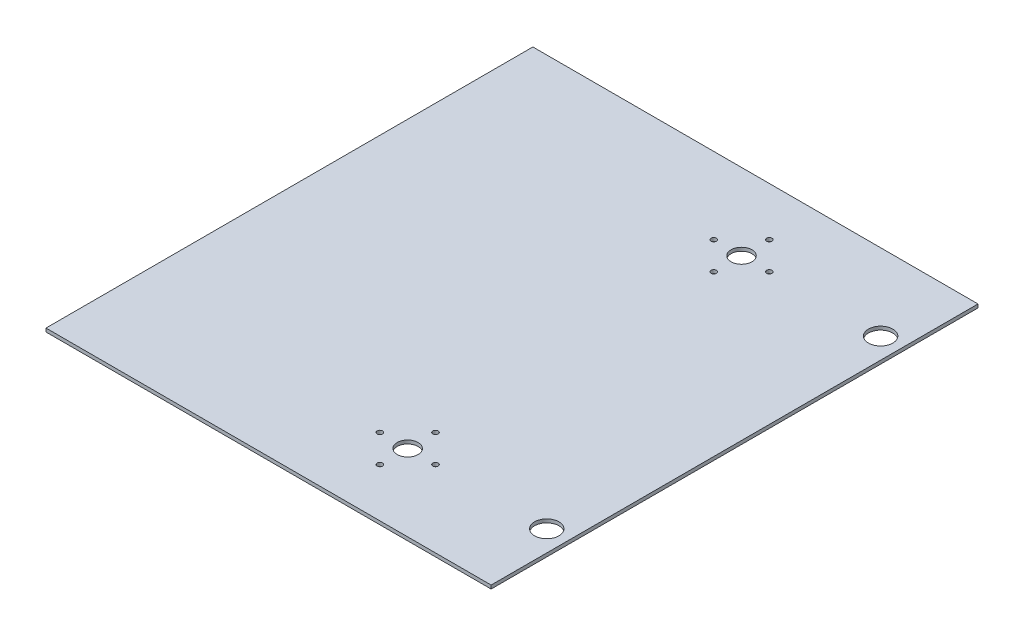
SolidWorks part; units mm, degrees
material "6061 Alloy"
ref_plane "Front Plane" through (0, 0, 0) normal (0, 0, 1) x (1, 0, 0)
ref_plane "Top Plane" through (0, 0, 0) normal (0, 1, 0) x (1, 0, 0)
ref_plane "Right Plane" through (0, 0, 0) normal (1, 0, 0) x (0, 0, -1)
sketch "Sketch1" plane through (0, 0, 0) normal (0, 1, 0) x (1, 0, 0)
  line L1 (203.2, -222.25) -> (-203.2, -222.25)
  line L2 (203.2, -222.25) -> (203.2, 222.25)
  line L3 (203.2, 222.25) -> (-203.2, 222.25)
  line L4 (-203.2, -222.25) -> (-203.2, 222.25)
  line L5 (203.2, -222.25) -> (-203.2, 222.25) construction
  line L6 (203.2, 222.25) -> (-203.2, -222.25) construction
  point P0 (0, 0)
  dimension "D1" = 406.4
  dimension "D2" = 444.5
extrude "Boss-Extrude1" add sketch "Sketch1" along normal blind 3.175
sketch "Sketch3" plane through (0, 3.175, 0) normal (0, 1, 0) x (1, 0, 0)
  arc A0 (66.675, -152.4) -> (47.625, -152.4) centre (57.15, -152.4) ccw construction
  arc A1 (47.625, -152.4) -> (66.675, -152.4) centre (57.15, -152.4) ccw construction
  arc A2 (66.675, -152.4) -> (47.625, -152.4) centre (57.15, -152.4) ccw
  arc A3 (47.625, -152.4) -> (66.675, -152.4) centre (57.15, -152.4) ccw
  arc A4 (66.675, 152.4) -> (47.625, 152.4) centre (57.15, 152.4) ccw construction
  arc A5 (47.625, 152.4) -> (66.675, 152.4) centre (57.15, 152.4) ccw construction
  arc A6 (66.675, 152.4) -> (47.625, 152.4) centre (57.15, 152.4) ccw
  arc A7 (47.625, 152.4) -> (66.675, 152.4) centre (57.15, 152.4) ccw
extrude "Cut-Extrude2" cut sketch "Sketch3" against normal through all
hole_wizard "#10 (0.1935) Diameter Hole1" positions "Sketch4" profile "Sketch5" hole size "#10" standard "ANSI Inch" end condition through all
sketch "Sketch4" plane through (0, 3.175, 0) normal (0, 1, 0) x (1, 0, 0)
  arc A0 (59.1693, -127) -> (55.1307, -127) centre (57.15, -127) ccw construction
  arc A1 (55.1307, -127) -> (59.1693, -127) centre (57.15, -127) ccw construction
  arc A2 (33.7693, -152.4) -> (29.7307, -152.4) centre (31.75, -152.4) ccw construction
  arc A3 (29.7307, -152.4) -> (33.7693, -152.4) centre (31.75, -152.4) ccw construction
  arc A4 (59.1693, -177.8) -> (55.1307, -177.8) centre (57.15, -177.8) ccw construction
  arc A5 (55.1307, -177.8) -> (59.1693, -177.8) centre (57.15, -177.8) ccw construction
  arc A6 (84.5693, -152.4) -> (80.5307, -152.4) centre (82.55, -152.4) ccw construction
  arc A7 (80.5307, -152.4) -> (84.5693, -152.4) centre (82.55, -152.4) ccw construction
  arc A8 (59.1693, -127) -> (55.1307, -127) centre (57.15, -127) ccw construction
  arc A9 (55.1307, -127) -> (59.1693, -127) centre (57.15, -127) ccw construction
  arc A10 (33.7693, -152.4) -> (29.7307, -152.4) centre (31.75, -152.4) ccw construction
  arc A11 (29.7307, -152.4) -> (33.7693, -152.4) centre (31.75, -152.4) ccw construction
  arc A12 (59.1693, -177.8) -> (55.1307, -177.8) centre (57.15, -177.8) ccw construction
  arc A13 (55.1307, -177.8) -> (59.1693, -177.8) centre (57.15, -177.8) ccw construction
  arc A14 (84.5693, -152.4) -> (80.5307, -152.4) centre (82.55, -152.4) ccw construction
  arc A15 (80.5307, -152.4) -> (84.5693, -152.4) centre (82.55, -152.4) ccw construction
  arc A16 (84.5693, 152.4) -> (80.5307, 152.4) centre (82.55, 152.4) ccw construction
  arc A17 (80.5307, 152.4) -> (84.5693, 152.4) centre (82.55, 152.4) ccw construction
  arc A18 (59.1693, 177.8) -> (55.1307, 177.8) centre (57.15, 177.8) ccw construction
  arc A19 (55.1307, 177.8) -> (59.1693, 177.8) centre (57.15, 177.8) ccw construction
  arc A20 (33.7693, 152.4) -> (29.7307, 152.4) centre (31.75, 152.4) ccw construction
  arc A21 (29.7307, 152.4) -> (33.7693, 152.4) centre (31.75, 152.4) ccw construction
  arc A22 (59.1693, 127) -> (55.1307, 127) centre (57.15, 127) ccw construction
  arc A23 (55.1307, 127) -> (59.1693, 127) centre (57.15, 127) ccw construction
  arc A24 (84.5693, 152.4) -> (80.5307, 152.4) centre (82.55, 152.4) ccw
  arc A25 (80.5307, 152.4) -> (84.5693, 152.4) centre (82.55, 152.4) ccw
  arc A26 (59.1693, 177.8) -> (55.1307, 177.8) centre (57.15, 177.8) ccw
  arc A27 (55.1307, 177.8) -> (59.1693, 177.8) centre (57.15, 177.8) ccw
  arc A28 (33.7693, 152.4) -> (29.7307, 152.4) centre (31.75, 152.4) ccw
  arc A29 (29.7307, 152.4) -> (33.7693, 152.4) centre (31.75, 152.4) ccw
  arc A30 (59.1693, 127) -> (55.1307, 127) centre (57.15, 127) ccw
  arc A31 (55.1307, 127) -> (59.1693, 127) centre (57.15, 127) ccw
  point P0 (57.15, -177.8)
  point P2 (31.75, -152.4)
  point P4 (57.15, -127)
  point P6 (82.55, -152.4)
  point P44 (57.15, 177.8)
  point P50 (31.75, 152.4)
  point P56 (57.15, 127)
  point P68 (82.55, 152.4)
sketch "Sketch5" plane through (57.15, 3.175, 177.8) normal (1, 0, 0) x (0, 0, 1)
  line L0 (0, 0) -> (0, 3.175)
  line L1 (0, 3.175) -> (2.4574, 3.175)
  line L2 (2.4574, 3.175) -> (2.4574, 0)
  line L5 (2.4574, 0) -> (0, 0)
  line L11 (0, -6.35) -> (0, 107.95) construction
  dimension "Thru Hole Dia." = 4.9149
  dimension "Thru Hole Depth" = 3.175
sketch "Sketch6" plane through (0, 3.175, 0) normal (0, 1, 0) x (1, 0, 0)
  line L0 (57.15, -114.3) -> (57.15, 114.3) construction
  line L1 (184.15, -152.4) -> (57.15, -152.4) construction
  line L2 (184.15, 152.4) -> (57.15, 152.4) construction
  line L3 (184.15, 152.4) -> (203.2, 152.4) construction
  line L4 (203.2, -222.25) -> (203.2, 222.25) construction
  circle A0 centre (57.15, -152.4) radius 38.1 construction
  circle A1 centre (57.15, 152.4) radius 38.1 construction
  circle A2 centre (184.15, -152.4) radius 38.1 construction
  circle A3 centre (184.15, 152.4) radius 38.1 construction
  dimension "D1" = 76.2
  dimension "D2" = 228.6
  dimension "D3" = 127
  dimension "D4" = 19.05
sketch "Sketch7" plane through (0, 3.175, 0) normal (0, 1, 0) x (1, 0, 0)
  circle A0 centre (184.15, -152.4) radius 11.1125
  circle A1 centre (184.15, 152.4) radius 11.1125
  dimension "D1" = 22.225
extrude "Cut-Extrude3" cut sketch "Sketch7" against normal through all
